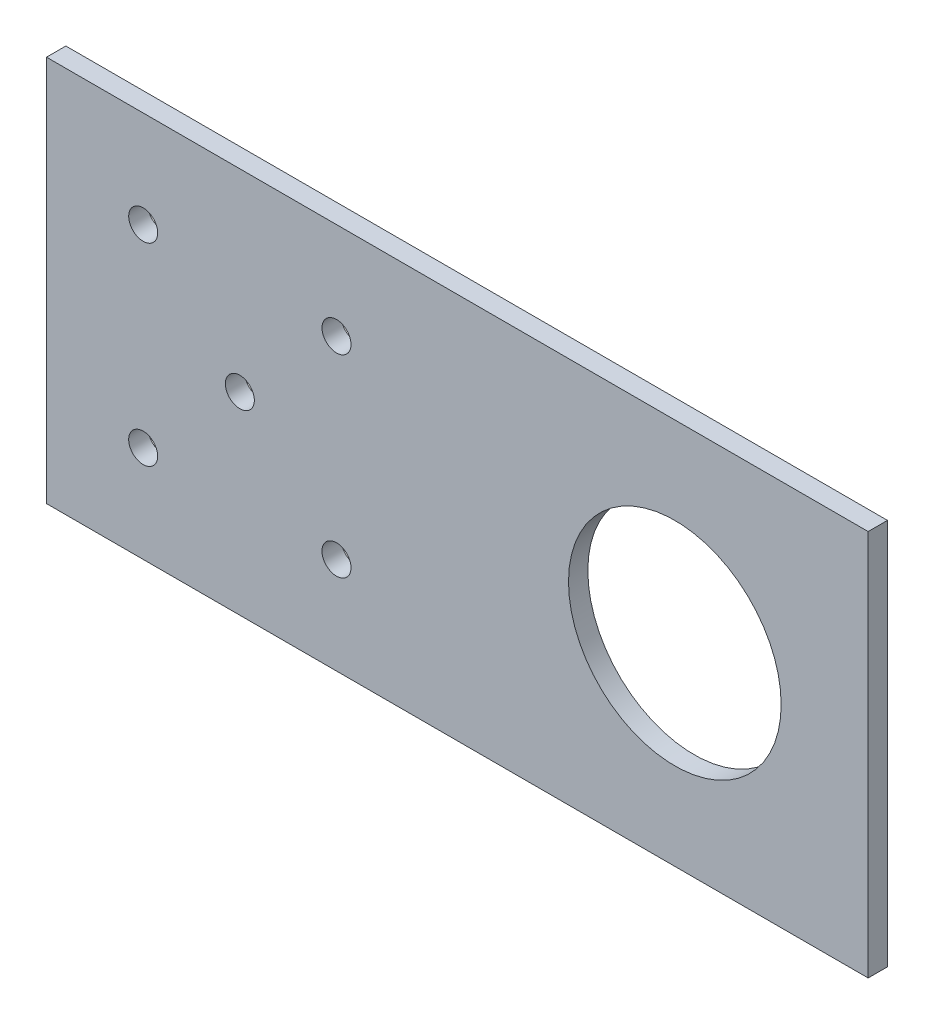
SolidWorks part; units mm, degrees
ref_plane "Front Plane" through (0, 0, 0) normal (0, 0, 1) x (1, 0, 0)
ref_plane "Top Plane" through (0, 0, 0) normal (0, 1, 0) x (1, 0, 0)
ref_plane "Right Plane" through (0, 0, 0) normal (1, 0, 0) x (0, 0, -1)
sketch "Sketch1" plane through (0, 0, 0) normal (0, 0, 1) x (1, 0, 0)
  line L1 (-42.5, 20) -> (42.5, 20)
  line L2 (-42.5, 20) -> (-42.5, -20)
  line L3 (-42.5, -20) -> (42.5, -20)
  line L4 (42.5, 20) -> (42.5, -20)
  line L5 (-42.5, 20) -> (42.5, -20) construction
  line L6 (-42.5, -20) -> (42.5, 20) construction
  point P0 (0, 0)
  dimension "D1" = 85
  dimension "D2" = 40
extrude "Boss-Extrude1" add sketch "Sketch1" along normal mid plane 2
sketch "Sketch2" plane through (0, 0, 1) normal (0, 0, 1) x (1, 0, 0)
  line L0 (1.1, 0) -> (-1.1, 0) construction
  line L1 (42.5, -20) -> (42.5, 20) construction
  line L2 (-32.5, 10) -> (-12.5, 10) construction
  line L3 (42.5, 20) -> (-42.5, 20) construction
  line L4 (-42.5, 20) -> (-42.5, -20) construction
  line L5 (-42.5, -20) -> (42.5, -20) construction
  circle A0 centre (22.5, 0) radius 11
  circle A1 centre (-22.5, 0) radius 1.5
  circle A2 centre (-32.5, 10) radius 1.5
  circle A3 centre (-12.5, 10) radius 1.5
  circle A4 centre (-12.5, -10) radius 1.5
  circle A5 centre (-32.5, -10) radius 1.5
  dimension "D1" = 22
  dimension "D3" = 3
  dimension "D2" = 20
  dimension "D6" = 20
  dimension "D7" = 10
  dimension "D8" = 10
  dimension "D9" = 20
  dimension "D10" = 10
  dimension "D4" = 2
  dimension "D5" = 2
extrude "Cut-Extrude1" cut sketch "Sketch2" against normal blind 2
